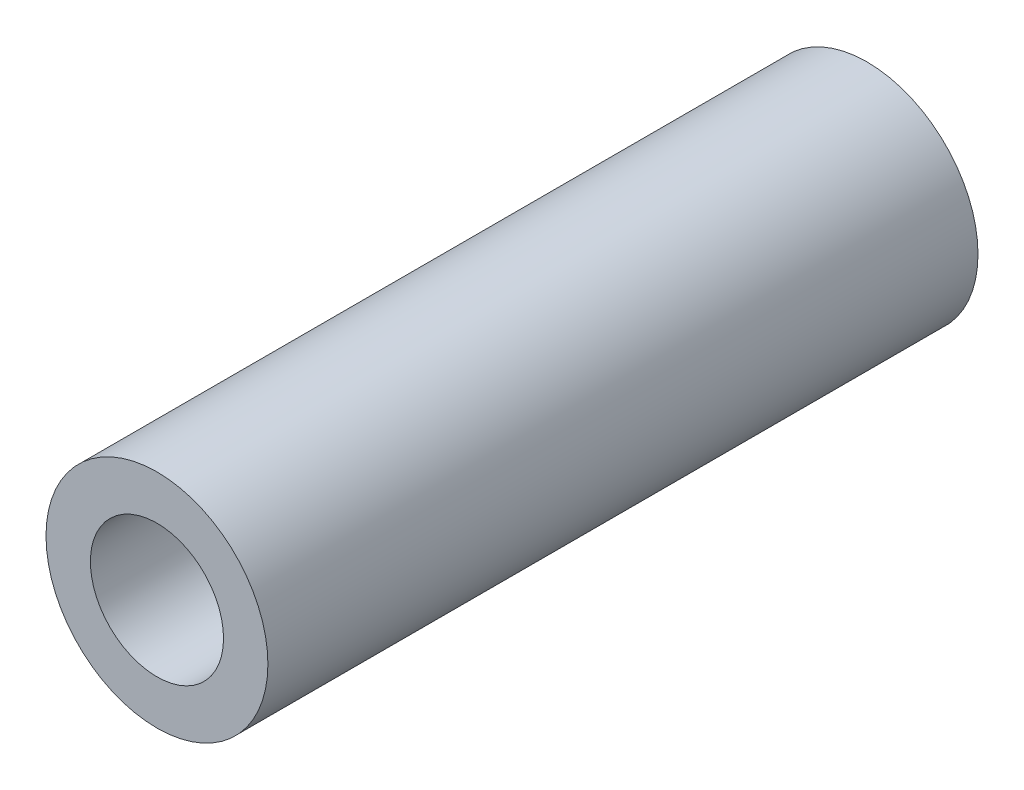
SolidWorks part; units mm, degrees
ref_plane "Plano frontal" through (0, 0, 0) normal (0, 0, 1) x (1, 0, 0)
ref_plane "Plano superior" through (0, 0, 0) normal (0, 1, 0) x (1, 0, 0)
ref_plane "Plano direito" through (0, 0, 0) normal (1, 0, 0) x (0, 0, -1)
sketch "Esboço1" plane through (0, 0, 0) normal (0, 0, 1) x (1, 0, 0)
  circle A0 centre (0, 0) radius 3
  circle A1 centre (0, 0) radius 5
  dimension "D1" = 6
  dimension "D2" = 10
extrude "Ressalto-extrusão1" add sketch "Esboço1" along normal blind 32
